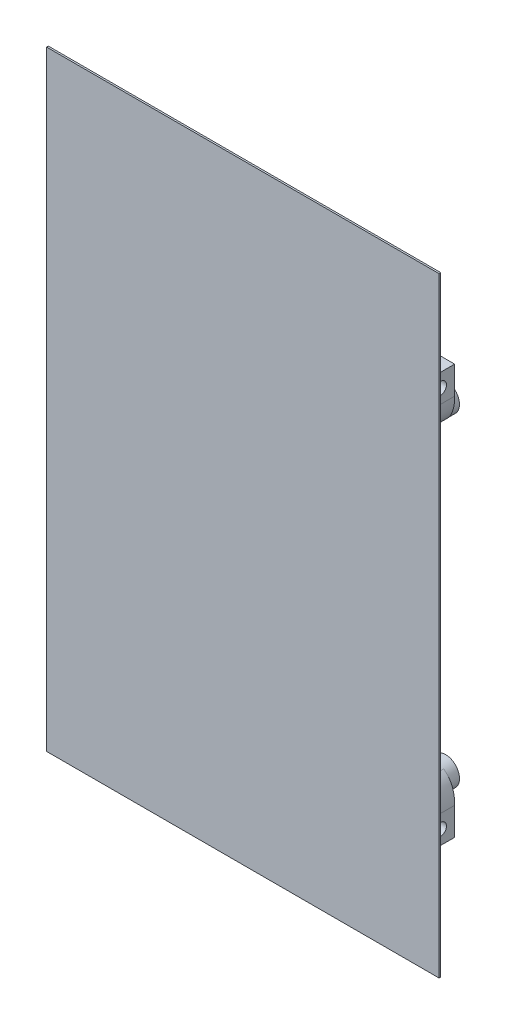
SolidWorks part; units mm, degrees
ref_plane "Front Plane" through (0, 0, 0) normal (0, 0, 1) x (1, 0, 0)
ref_plane "Top Plane" through (0, 0, 0) normal (0, 1, 0) x (1, 0, 0)
ref_plane "Right Plane" through (0, 0, 0) normal (1, 0, 0) x (0, 0, -1)
sketch "Sketch1" plane through (0, 0, 0) normal (0, 0, 1) x (1, 0, 0)
  line L1 (109, 161.3091) -> (-4, 161.3091)
  line L2 (109, 161.3091) -> (109, -14.3091)
  line L3 (109, -14.3091) -> (-4, -14.3091)
  line L4 (-4, 161.3091) -> (-4, -14.3091)
extrude "Boss-Extrude1" add sketch "Sketch1" along normal blind 0.5
sketch "Sketch2" plane through (0, 0, 0) normal (0, 0, -1) x (-1, 0, 0)
  circle A0 centre (-5.6, 26.85) radius 2 construction
  circle A1 centre (-99.4, 26.85) radius 2 construction
  circle A2 centre (-99.4, 120.15) radius 2 construction
  circle A3 centre (-5.6, 120.15) radius 2 construction
  circle A4 centre (-5.6, 26.85) radius 2
  circle A5 centre (-99.4, 26.85) radius 2
  circle A6 centre (-99.4, 120.15) radius 2
  circle A7 centre (-5.6, 120.15) radius 2
  circle A8 centre (-5.6, 120.15) radius 4
  circle A9 centre (-5.6, 26.85) radius 4
  circle A10 centre (-99.4, 26.85) radius 4
  circle A11 centre (-99.4, 120.15) radius 4
  dimension "D1" = 8
extrude "Boss-Extrude2" add sketch "Sketch2" along normal up to surface (11 mm away)
sketch "Sketch3" plane through (0, 0, 0) normal (0, 0, -1) x (-1, 0, 0)
  line L0 (-99.4, 120.15) -> (-5.6, 120.15) construction
  line L1 (-7.3321, 123.15) -> (-8.2458, 123.15)
  line L2 (-9.0641, 120.15) -> (-7.3321, 117.15)
  line L3 (-7.3321, 117.15) -> (-3.8679, 117.15)
  line L4 (-3.8679, 117.15) -> (-2.1359, 120.15)
  line L5 (-2.1359, 120.15) -> (-3.8679, 123.15)
  line L6 (-3.8679, 123.15) -> (-7.3321, 123.15)
  line L7 (-7.3321, 123.15) -> (-9.0641, 120.15)
  line L8 (-7.3321, 117.15) -> (-8.2458, 117.15)
  line L9 (-52.5, 161.3091) -> (-52.5, -14.3091) construction
  line L10 (-109, 161.3091) -> (4, 161.3091) construction
  line L11 (4, -14.3091) -> (-109, -14.3091) construction
  line L12 (-97.6679, 117.15) -> (-96.7542, 117.15)
  line L13 (-97.6679, 123.15) -> (-95.9359, 120.15)
  line L14 (-95.9359, 120.15) -> (-97.6679, 117.15)
  line L15 (-97.6679, 117.15) -> (-101.1321, 117.15)
  line L16 (-101.1321, 117.15) -> (-102.8641, 120.15)
  line L17 (-102.8641, 120.15) -> (-101.1321, 123.15)
  line L18 (-101.1321, 123.15) -> (-97.6679, 123.15)
  line L19 (-97.6679, 123.15) -> (-96.7542, 123.15)
  line L20 (-109, 73.5) -> (4, 73.5) construction
  line L21 (-109, -14.3091) -> (-109, 161.3091) construction
  line L22 (4, 161.3091) -> (4, -14.3091) construction
  line L23 (-7.3321, 29.85) -> (-8.2458, 29.85)
  line L24 (-7.3321, 29.85) -> (-3.8679, 29.85)
  line L25 (-9.0641, 26.85) -> (-7.3321, 29.85)
  line L26 (-2.1359, 26.85) -> (-3.8679, 23.85)
  line L27 (-3.8679, 29.85) -> (-2.1359, 26.85)
  line L28 (-7.3321, 23.85) -> (-9.0641, 26.85)
  line L29 (-3.8679, 23.85) -> (-7.3321, 23.85)
  line L30 (-7.3321, 23.85) -> (-8.2458, 23.85)
  line L31 (-97.6679, 23.85) -> (-96.7542, 23.85)
  line L32 (-101.1321, 23.85) -> (-97.6679, 23.85)
  line L33 (-102.8641, 26.85) -> (-101.1321, 23.85)
  line L34 (-101.1321, 29.85) -> (-102.8641, 26.85)
  line L35 (-97.6679, 29.85) -> (-101.1321, 29.85)
  line L36 (-95.9359, 26.85) -> (-97.6679, 29.85)
  line L37 (-97.6679, 23.85) -> (-95.9359, 26.85)
  line L38 (-97.6679, 29.85) -> (-96.7542, 29.85)
  circle A0 centre (-5.6, 120.15) radius 3 construction
  circle A1 centre (-5.6, 120.15) radius 4 construction
  circle A2 centre (-5.6, 120.15) radius 4 construction
  circle M15 centre (-99.4, 120.15) radius 4
  circle M16 centre (-99.4, 26.85) radius 4
  circle M17 centre (-5.6, 26.85) radius 4
  circle M18 centre (-5.6, 120.15) radius 4
  dimension "D1" = 6
extrude "Cut-Extrude1" cut sketch "Sketch3" along normal blind 3 contours L18 L17 L16 L15 L14 L13 | L19 L13 L14 L12 M15 | L6 L7 L2 L3 L4 L5 | L8 L2 L7 L1 M18 | L29 L26 L27 L24 L25 L28 | L30 L28 L25 L23 M17 | L32 L37 L36 L35 L34 L33 | L38 L36 L37 L31 M16 region at (8.2536, 121.6821, 0) region at (5.6, 120.15, 0) region at (96.7464, 118.6179, 0) region at (99.4, 120.15, 0) region at (8.2536, 28.3821, 0) region at (5.6, 26.85, 0) region at (96.7464, 25.3179, 0) region at (99.4, 26.85, 0)
sketch "Sketch4" plane through (0, 0, 0) normal (0, 0, -1) x (-1, 0, 0)
  line L0 (-105, -14.3091) -> (-105, 12.5) construction
  line L1 (-105, 14.5) -> (-100, 14.5)
  line L2 (-105, 14.5) -> (-105, 22.5)
  line L3 (-105, 22.5) -> (-100, 22.5)
  line L4 (-100, 14.5) -> (-100, 22.5)
  line L5 (-100, 18.5) -> (-105, 18.5) construction
  line L7 (-104.2951, 26.85) -> (-99.4, 26.85) construction
  line L8 (-100, 22.5) -> (-100, 22.8953)
  line L15 (-109, 18.5) -> (-105, 18.5) construction
  arc A0 (-96.7542, 29.85) -> (-96.7542, 23.85) centre (-99.4, 26.85) ccw construction
  circle A1 centre (-99.4, 26.85) radius 4 construction
  spline S1 degree 3 poles (-105, 22.5) (-105, 25.5429) (-104.3608, 28.0669) (-101.8496, 30.0122) knots 0 0 0 0 1 1 1 1
  arc M10 (-96.7542, 23.85) -> (-96.7542, 29.85) centre (-99.4, 26.85) cw
  dimension "D1" = 8
  dimension "D2" = 5
extrude "Boss-Extrude3" add sketch "Sketch4" along normal blind 8 contours L1 L4 L3 L2 | S1 L3 L8 M10 region at (102.5, 18.5, 0) region at (103.3471, 24.4202, 0)
sketch "Sketch5" plane through (100, 0, 0) normal (-1, 0, 0) x (0, 0, 1)
  circle A1 centre (-3.8964, 18.5) radius 1.75
  circle A2 centre (-3.8964, 18.5) radius 2.9 construction
  dimension "D1" = 3.5
extrude "Cut-Extrude2" cut sketch "Sketch5" against normal up to next
sketch "Sketch6" plane through (100, 0, 0) normal (-1, 0, 0) x (0, 0, 1)
  line L1 (-3.8964, 21.9641) -> (-6.8964, 20.2321)
  line L2 (-6.8964, 20.2321) -> (-6.8964, 16.7679)
  line L3 (-6.8964, 16.7679) -> (-3.8964, 15.0359)
  line L4 (-3.8964, 15.0359) -> (-0.8964, 16.7679)
  line L5 (-0.8964, 16.7679) -> (-0.8964, 20.2321)
  line L6 (-0.8964, 20.2321) -> (-3.8964, 21.9641)
  circle A0 centre (-3.8964, 18.5) radius 3 construction
  dimension "D1" = 6
extrude "Cut-Extrude3" cut sketch "Sketch6" against normal blind 2.5
ref_plane "Plane1" through (0, 73.5, 0) normal (0, -1, 0) x (-1, 0, 0)
ref_plane "Plane2" through (52.5, 0, 0) normal (-1, 0, 0) x (0, 0, 1)
mirror "Mirror1" about plane through (52.5, 0, 0) normal (-1, 0, 0) of "Cut-Extrude3", "Cut-Extrude2", "Boss-Extrude3"
mirror "Mirror2" about plane through (0, 73.5, 0) normal (0, -1, 0) of "Cut-Extrude3", "Cut-Extrude2", "Boss-Extrude3", "Mirror1"
sketch "Sketch7" plane through (0, 0, 0) normal (0, 0, -1) x (-1, 0, 0)
  line L0 (-109, 73.5) -> (4, 73.5) construction
  line L1 (-109, -14.3091) -> (-109, 161.3091) construction
  line L2 (4, 161.3091) -> (4, -14.3091) construction
  line L3 (-52.5, -14.3091) -> (-52.5, 161.3091) construction
  line L4 (0, -14.3091) -> (-105, -14.3091) construction
  line L5 (0, 161.3091) -> (-105, 161.3091) construction
  line L6 (-109, -14.3091) -> (4, 161.3091) construction
  line L7 (4, -14.3091) -> (-109, 161.3091) construction
  line L8 (-91.1065, 13.5) -> (-13.8935, 13.5) construction
  line L9 (-91.1065, 133.5) -> (-13.8935, 133.5) construction
  line L10 (-91.1065, 13.5) -> (-91.1065, 133.5) construction
  line L11 (-13.8935, 13.5) -> (-13.8935, 133.5) construction
  line L12 (-93.6065, 11) -> (-11.3935, 11)
  line L13 (-11.3935, 11) -> (-11.3935, 136)
  line L14 (-93.6065, 136) -> (-11.3935, 136)
  line L15 (-93.6065, 11) -> (-93.6065, 136)
  line L16 (-109, 71) -> (4, 71)
  line L17 (6.1024, -12.9563) -> (-106.8976, 162.6619)
  line L18 (-50, -14.3091) -> (-50, 161.3091)
  line L19 (-106.8976, -15.6619) -> (6.1024, 159.9563)
  line L20 (-88.6065, 16) -> (-16.3935, 16)
  line L21 (-16.3935, 16) -> (-16.3935, 131)
  line L22 (-88.6065, 131) -> (-16.3935, 131)
  line L23 (-88.6065, 16) -> (-88.6065, 131)
  line L24 (-109, 76) -> (4, 76)
  line L25 (1.8976, -15.6619) -> (-111.1024, 159.9563)
  line L26 (-55, -14.3091) -> (-55, 161.3091)
  line L27 (-111.1024, -12.9563) -> (1.8976, 162.6619)
  dimension "D1" = 60
  dimension "D2" = 2.5
  dimension "D3" = 2.5
extrude "Boss-Extrude4" add sketch "Sketch7" along normal blind 0.5 contours L12 L26 L20 L19 | L27 L15 L12 L19 L20 L23 | L15 L27 L23 L16 | L27 L23 L20 L19 L26 L16 | L24 L15 L16 L23 | L16 L27 L25 L24 L23 | L23 L25 L15 L24 | L25 L23 L22 L17 L14 L15 | L24 L26 L17 L22 L23 L25 | L22 L26 L14 L17 | L26 L22 L18 L14 | L17 L27 L18 L22 L26 | L22 L27 L14 L18 | L27 L22 L21 L19 L13 L14 | L27 L18 L24 L19 L21 L22 | L21 L24 L13 L19 | L24 L21 L16 L13 | L24 L19 L17 L16 L21 | L21 L17 L13 L16 | L25 L20 L21 L17 L16 L18 | L26 L20 L18 L25 L19 | L26 L12 L18 L20 | L12 L25 L20 L18 | L25 L12 L13 L17 L21 L20 | L26 L19 L25 L16 | L27 L16 L26 L25 | L26 L16 L25 | L25 L27 L26 L24 | L27 L25 L26 | L26 L27 L24 | L24 L27 L17 L26 | L27 L17 L24 L18 | L24 L18 L17 L19 | L19 L18 L16 L17 | L19 L16 L18 | L25 L18 L16 L19 | L25 L19 L16 | L27 L26 L25 L16 L19 L18 L17 L24 | L27 L24 L17 | L24 L17 L18 | L18 L19 L17 region at (90.4529, 15.002, 0) region at (71.5799, 13.4595, 0) region at (91.1677, 44.5125, 0) region at (52.5, 13.5, 0) region at (71.8032, 43.5, 0) region at (91.1065, 73.5, 0) region at (33.4201, 13.4595, 0) region at (52.5, 41.4809, 0) region at (54.1143, 68.5681, 0) region at (91.1677, 102.4875, 0) region at (72.4385, 73.5, 0) region at (55.7555, 71.9147, 0) region at (14.5471, 15.002, 0) region at (52.5, 70.2933, 0) region at (50.8857, 68.5681, 0) region at (54.6214, 71.5884, 0) region at (90.4529, 131.998, 0) region at (55.1576, 73.5, 0) region at (55.7555, 75.0853, 0) region at (33.1968, 43.5, 0) region at (50.3786, 71.5884, 0) region at (52.5, 73.5, 0) region at (71.8032, 103.5, 0) region at (54.6214, 75.4116, 0) region at (13.8323, 44.5125, 0) region at (49.2445, 71.9147, 0) region at (49.8424, 73.5, 0) region at (71.5799, 133.5405, 0) region at (54.1143, 78.4319, 0) region at (52.5, 76.7067, 0) region at (13.8935, 73.5, 0) region at (32.5615, 73.5, 0) region at (49.2445, 75.0853, 0) region at (50.3786, 75.4116, 0) region at (52.5, 133.5, 0) region at (52.5, 105.5191, 0) region at (50.8857, 78.4319, 0) region at (13.8323, 102.4875, 0) region at (33.1968, 103.5, 0) region at (33.4201, 133.5405, 0) region at (14.5471, 131.998, 0)
